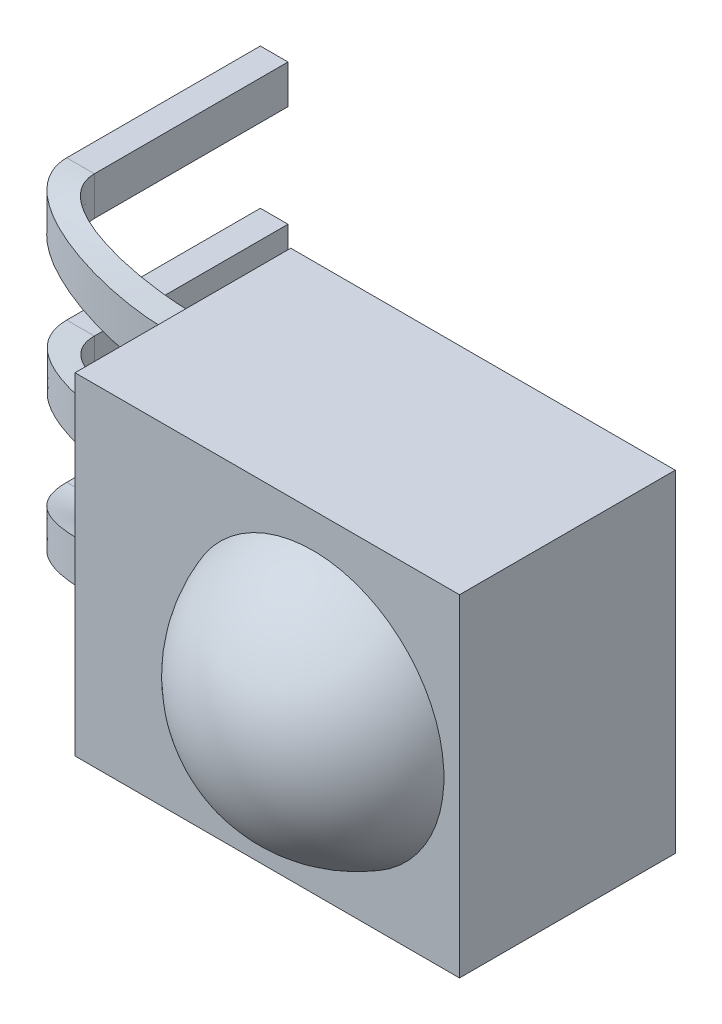
SolidWorks part; units mm, degrees
other "Детальный элемент1"
ref_plane "Спереди" through (0, 0, 0) normal (0, 0, 1) x (1, 0, 0)
ref_plane "Сверху" through (0, 0, 0) normal (0, 1, 0) x (1, 0, 0)
ref_plane "Справа" through (0, 0, 0) normal (1, 0, 0) x (0, 0, -1)
sketch "Эскиз1" plane through (0, 0, 0) normal (0, 0, 1) x (1, 0, 0)
  line L1 (-4.3, -3) -> (2.65, -3)
  line L2 (-4.3, -3) -> (-4.3, 3)
  line L3 (-4.3, 3) -> (2.65, 3)
  line L4 (2.65, -3) -> (2.65, 3)
  point P0 (0, 0)
  dimension "D1" = 6
  dimension "D2" = 6.95
  dimension "D3" = 2.65
  dimension "D4" = 3
extrude "Бобышка-Вытянуть1" add sketch "Эскиз1" along normal blind 3.9
sketch "Эскиз5" plane through (0, 0, 0) normal (0, 0, 1) x (1, 0, 0)
  line L1 (-7.85, 2.89) -> (-7.35, 2.89)
  line L2 (-7.85, 2.89) -> (-7.85, 2.19)
  line L3 (-7.85, 2.19) -> (-7.35, 2.19)
  line L4 (-7.35, 2.89) -> (-7.35, 2.19)
  line L5 (-7.85, 2.89) -> (-7.35, 2.19) construction
  line L6 (-7.85, 2.19) -> (-7.35, 2.89) construction
  line L7 (-7.35, 0.35) -> (-7.85, 0.35)
  line L8 (-7.35, 0.35) -> (-7.35, -0.35)
  line L9 (-7.35, -0.35) -> (-7.85, -0.35)
  line L10 (-7.85, 0.35) -> (-7.85, -0.35)
  line L11 (-7.35, 0.35) -> (-7.85, -0.35) construction
  line L12 (-7.35, -0.35) -> (-7.85, 0.35) construction
  line L13 (-7.35, -2.19) -> (-7.85, -2.19)
  line L14 (-7.35, -2.19) -> (-7.35, -2.89)
  line L15 (-7.35, -2.89) -> (-7.85, -2.89)
  line L16 (-7.85, -2.19) -> (-7.85, -2.89)
  line L17 (-7.35, -2.19) -> (-7.85, -2.89) construction
  line L18 (-7.35, -2.89) -> (-7.85, -2.19) construction
  point P0 (-7.6, 2.54)
  point P5 (-7.6, 0)
  point P10 (-7.6, -2.54)
  dimension "D1" = 0.7
  dimension "D2" = 0.5
  dimension "D3" = 2.54
  dimension "D4" = 2.54
  dimension "D5" = 7.6
extrude "Бобышка-Вытянуть2" add sketch "Эскиз5" along normal blind 0.5 and the other way blind 3 separate body
sketch "Эскиз6" plane through (-4.3, 0, 0) normal (-1, 0, 0) x (0, 0, 1)
  line L0 (0, 3) -> (0, -3) construction
  line L1 (1.8, 0.4) -> (1.3, 0.4)
  line L2 (1.8, 0.4) -> (1.8, -0.4)
  line L3 (1.8, -0.4) -> (1.3, -0.4)
  line L4 (1.3, 0.4) -> (1.3, -0.4)
  line L5 (1.8, 0.4) -> (1.3, -0.4) construction
  line L6 (1.8, -0.4) -> (1.3, 0.4) construction
  line L7 (1.3, -1.6) -> (1.8, -1.6)
  line L8 (1.3, -1.6) -> (1.3, -2.4)
  line L9 (1.3, -2.4) -> (1.8, -2.4)
  line L10 (1.8, -1.6) -> (1.8, -2.4)
  line L11 (1.3, -1.6) -> (1.8, -2.4) construction
  line L12 (1.3, -2.4) -> (1.8, -1.6) construction
  line L13 (1.3, 1.6) -> (1.8, 1.6)
  line L14 (1.3, 1.6) -> (1.3, 2.4)
  line L15 (1.3, 2.4) -> (1.8, 2.4)
  line L16 (1.8, 1.6) -> (1.8, 2.4)
  line L17 (1.3, 1.6) -> (1.8, 2.4) construction
  line L18 (1.3, 2.4) -> (1.8, 1.6) construction
  point P0 (1.55, 0)
  point P5 (1.55, -2)
  point P10 (1.55, 2)
  dimension "D1" = 2
  dimension "D2" = 2
  dimension "D3" = 0.5
  dimension "D4" = 0.8
  dimension "D5" = 1.55
extrude "Бобышка-Вытянуть3" add sketch "Эскиз6" along normal blind 0.5
loft "По сечениям1" add section face at (-4.8, 2, 1.55) section face at (-7.6, 2.54, 0.5) start constraint normal to profile start tangent length 1 end constraint normal to profile end tangent length 1 connector at (-4.8, 1.6, 1.3) connector at (-7.35, 2.19, 0.5)
loft "По сечениям2" add section face at (-7.6, 0, 0.5) section face at (-4.8, 0, 1.55) start constraint normal to profile start tangent length 1 end constraint normal to profile end tangent length 1 connector at (-7.35, -0.35, 0.5) connector at (-4.8, -0.4, 1.3)
loft "По сечениям3" add section face at (-7.6, -2.54, 0.5) section face at (-4.8, -2, 1.55) start constraint normal to profile start tangent length 1 end constraint normal to profile end tangent length 1 connector at (-7.35, -2.19, 0.5) connector at (-4.8, -1.6, 1.3)
ref_plane "Плоскость1" through (0, 0, 3.1) normal (0, 0, 1) x (1, 0, 0)
sketch "Эскиз7" plane through (0, 0, 3.1) normal (0, 0, 1) x (1, 0, 0)
  line L0 (0, 2.5) -> (0, -2.5)
  arc A1 (0, -2.5) -> (0, 2.5) centre (0, 0) ccw
  dimension "D2" = 2.5
  dimension "D1" = 5
revolve "Повернуть2" add sketch "Эскиз7" angle 360 about L0
